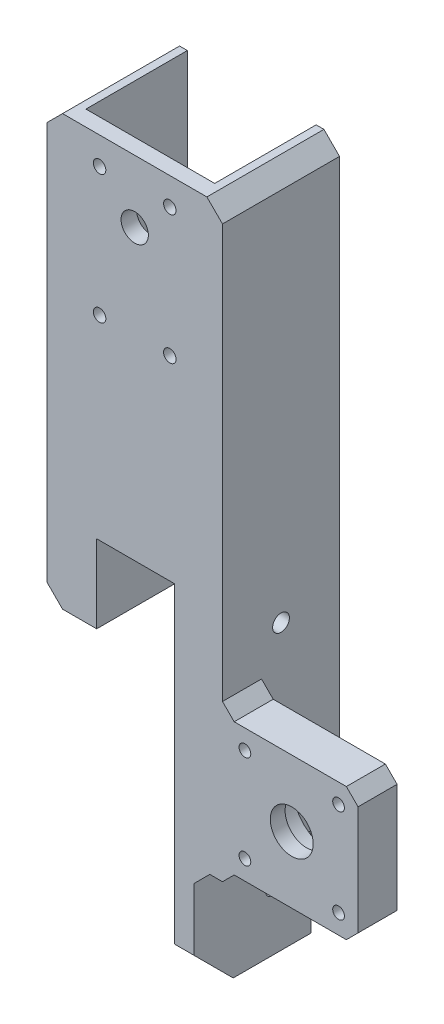
SolidWorks part; units mm, degrees
ref_plane "前视基准面" through (0, 0, 0) normal (0, 0, 1) x (1, 0, 0)
ref_plane "上视基准面" through (0, 0, 0) normal (0, 1, 0) x (1, 0, 0)
ref_plane "右视基准面" through (0, 0, 0) normal (1, 0, 0) x (0, 0, -1)
sketch "草图1" plane through (0, 0, 0) normal (0, 0, 1) x (1, 0, 0)
  line L0 (7.5, 40) -> (25.5, 7) construction
  line L1 (0, 0) -> (33, 0)
  line L2 (0, 0) -> (0, 47)
  line L3 (0, 47) -> (33, 47)
  line L4 (33, 0) -> (33, 47)
  circle A0 centre (7.5, 40) radius 1.6
  circle A1 centre (25.5, 40) radius 1.6
  circle A2 centre (7.5, 7) radius 1.6
  circle A3 centre (25.5, 7) radius 1.6
  circle A4 centre (16.5, 31) radius 3.5
  point P13 (0, 23.5)
  point P14 (16.5, 23.5)
  point P15 (16.5, 47)
  dimension "D5" = 3.2
  dimension "D6" = 7
  dimension "D1" = 18
  dimension "D2" = 33
  dimension "D3" = 33
  dimension "D4" = 47
  dimension "D7" = 9
extrude "凸台-拉伸1" add sketch "草图1" along normal blind 4
sketch "草图3" plane through (0, 0, 0) normal (0, 0, -1) x (-1, 0, 0)
  line L0 (0, -38) -> (-33, -38)
  line L1 (0, 47) -> (6, 47)
  line L2 (0, 47) -> (0, -38)
  line L4 (6, 47) -> (6, -63)
  line L5 (-33, 47) -> (-39, 47)
  line L6 (-33, 47) -> (-33, -38)
  line L8 (-39, 47) -> (-39, -63)
  line L9 (6, -63) -> (-6.25, -63)
  line L10 (-6.25, -63) -> (-6.25, -43)
  line L11 (-6.25, -43) -> (-26.75, -43)
  line L12 (-26.75, -43) -> (-26.75, -63)
  line L13 (-26.75, -63) -> (-39, -63)
  point P2 (-16.5, -38)
  point P14 (-16.5, -43)
  dimension "D1" = 6
  dimension "D2" = 6
  dimension "D3" = 25
  dimension "D4" = 110
  dimension "D5" = 20.5
  dimension "D6" = 20
extrude "凸台-拉伸2" add sketch "草图3" against normal blind 30
sketch "草图4" plane through (0, 0, 0) normal (0, 0, -1) x (-1, 0, 0)
  line L1 (-33, -38) -> (0, -38)
  line L2 (-33, -38) -> (-33, 0)
  line L3 (-33, 0) -> (0, 0)
  line L4 (0, -38) -> (0, 0)
extrude "凸台-拉伸3" add sketch "草图4" against normal up to surface (4 mm away) up to face at (16.5, 23.5, 4)
sketch "草图6" plane through (0, 0, 0) normal (0, 0, -1) x (-1, 0, 0)
  line L0 (-26.75, -63) -> (-26.75, -103)
  line L1 (-26.75, -63) -> (-26.75, -173) construction
  line L2 (-26.75, -103) -> (-76.75, -103)
  line L3 (-76.75, -103) -> (-76.75, -63)
  line L4 (-76.75, -63) -> (-26.75, -63)
  circle A0 centre (-56.75, -83) radius 5.5
  circle A1 centre (-68.75, -95) radius 1.5
  circle A2 centre (-68.75, -71) radius 1.5
  circle A3 centre (-44.75, -95) radius 1.5
  circle A4 centre (-44.75, -71) radius 1.5
  dimension "D3" = 11
  dimension "D10" = 3
  dimension "D1" = 40
  dimension "D2" = 50
  dimension "D4" = 20
  dimension "D5" = 20
  dimension "D6" = 12
  dimension "D7" = 12
  dimension "D8" = 12
  dimension "D9" = 12
extrude "凸台-拉伸4" add sketch "草图6" against normal through all
sketch "草图7" plane through (0, 0, 30) normal (0, 0, 1) x (1, 0, 0)
  line L1 (76.75, -103) -> (39, -103)
  line L2 (76.75, -103) -> (76.75, -63)
  line L3 (76.75, -63) -> (39, -63)
  line L4 (39, -103) -> (39, -63)
extrude "切除-拉伸1" cut sketch "草图7" against normal blind 20 contours L1 L4 L3 L2
sketch "草图8" plane through (0, 0, 10) normal (0, 0, 1) x (1, 0, 0)
  circle A0 centre (56.75, -83) radius 9.75
  dimension "D1" = 19.5
extrude "切除-拉伸2" cut sketch "草图8" against normal blind 6.2
sketch "草图10" plane through (-6, 0, 0) normal (-1, 0, 0) x (0, 0, 1)
  line L0 (30, -63) -> (0, -63) construction
  circle A0 centre (15, -53) radius 2.15
  point P4 (15, -63)
  dimension "D2" = 4.3
  dimension "D1" = 10
extrude "切除-拉伸4" cut sketch "草图10" against normal through all contours A0
sketch "草图11" plane through (26.75, 0, 0) normal (-1, 0, 0) x (0, 0, 1)
  line L1 (30, -103) -> (0, -103)
  line L2 (30, -103) -> (30, -133)
  line L3 (30, -133) -> (0, -133)
  line L4 (0, -103) -> (0, -133)
  circle A3 centre (20, -118) radius 1.7
  dimension "D5" = 20
  dimension "D1" = 15
  dimension "D3" = 3.4
  dimension "D2" = 30
extrude "凸台-拉伸5" add sketch "草图11" against normal blind 5
sketch "草图12" plane through (0, 0, 10) normal (0, 0, 1) x (1, 0, 0)
  line L0 (39, -103) -> (76.75, -103)
  line L5 (76.75, -103) -> (76.75, -63)
  line L6 (76.75, -63) -> (39, -63)
  line L7 (39, -63) -> (39, -66)
  line L8 (39, 47) -> (39, -103) construction
  line L9 (39, -66) -> (73.75, -66)
  line L10 (73.75, -66) -> (73.75, -100)
  line L11 (73.75, -100) -> (39, -100)
  line L12 (39, -100) -> (39, -103)
  dimension "D1" = 3
  dimension "D2" = 3
  dimension "D3" = 3
extrude "切除-拉伸5" cut sketch "草图12" against normal blind 20
chamfer "倒角1" distance 4 angle 45 4 edges at (-6, -63, 15) (-6, 47, 15) (39, 47, 15) (31.75, -103, 15)
chamfer "倒角2" distance 3 angle 45 4 edges at (39, -66, 5) (73.75, -66, 5) (73.75, -100, 5) (39, -100, 5)
chamfer "倒角3" distance 10 angle 45 1 edges at (29.25, -133, 0)
mirror "镜向1" about plane through (0, 0, 0) normal (0, 0, -1) of bodies 118
sketch "草图13" plane through (0, 0, 30) normal (0, 0, 1) x (1, 0, 0)
  line L1 (94.2558, -134.7858) -> (-38.668, -134.7858)
  line L2 (94.2558, -134.7858) -> (94.2558, 54.181)
  line L3 (94.2558, 54.181) -> (-38.668, 54.181)
  line L4 (-38.668, -134.7858) -> (-38.668, 54.181)
extrude "切除-拉伸6" cut sketch "草图13" against normal up to vertex (30 mm away) and the other way through all up to point (26.75, -123, 0)
sketch "草图14" plane through (6.25, 0, 0) normal (1, 0, 0) x (0, 0, -1)
  line L4 (0, -43) -> (0, -63)
  line L5 (0, -63) -> (30, -63)
  line L6 (30, -63) -> (30, -43)
  line L7 (30, -43) -> (0, -43)
  line L8 (0, -43) -> (0, -63)
  line L9 (0, -63) -> (30, -63)
  line L10 (30, -63) -> (30, -43)
  line L11 (30, -43) -> (0, -43)
  circle A0 centre (15, -53) radius 2.15 construction
  circle A1 centre (15, -53) radius 2.15
  dimension "D1" = 0
extrude "凸台-拉伸6" add sketch "草图14" along normal blind 0.5
